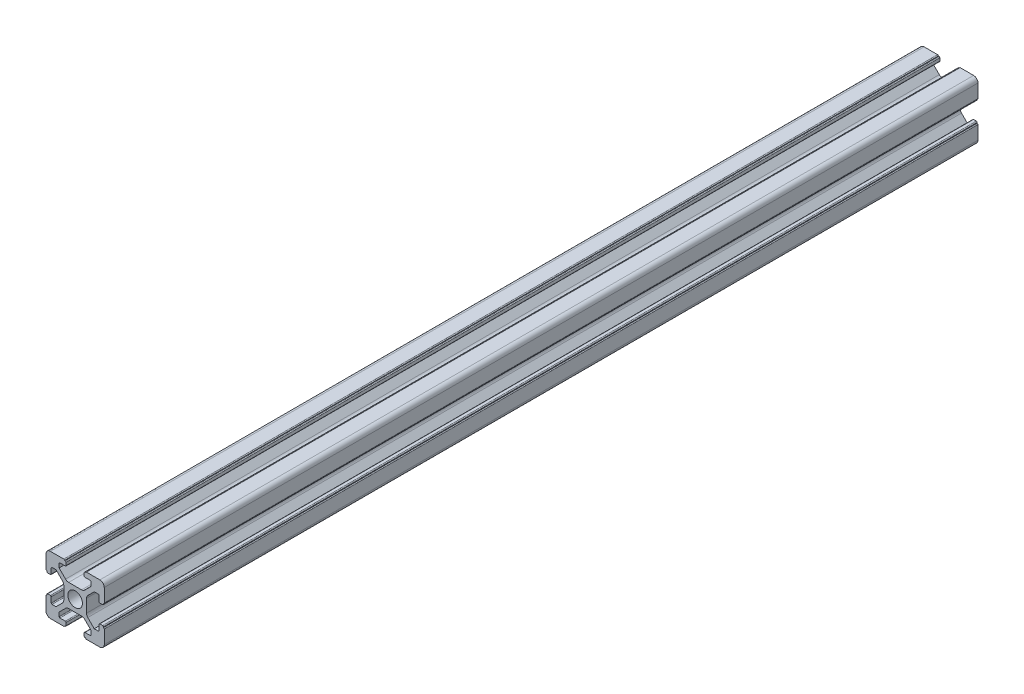
SolidWorks part; units mm, degrees
material "1060 Alloy"
ref_plane "Front Plane" through (0, 0, 0) normal (0, 0, 1) x (1, 0, 0)
ref_plane "Top Plane" through (0, 0, 0) normal (0, 1, 0) x (1, 0, 0)
ref_plane "Right Plane" through (0, 0, 0) normal (1, 0, 0) x (0, 0, -1)
sketch "Sketch1" plane through (0, 0, 0) normal (0, 0, 1) x (1, 0, 0)
  line L0 (3.8995, 3.9005) -> (10.4604, 10.4604) construction
  line L2 (-3.9002, 2.2177) -> (-3.9002, -2.2208)
  line L5 (-3.9005, 3.899) -> (3.9001, -3.8986) construction
  line L6 (-3.9, -3.901) -> (3.8995, 3.9005) construction
  line L7 (-0.0002, 10) -> (-0.0002, -9.9996) construction
  line L8 (-0.0002, -9.9996) -> (-0.0002, 10) construction
  line L9 (5.5006, 6.5619) -> (3.2793, 4.3405)
  line L14 (-10.0002, 9.9996) -> (9.9994, -10) construction
  line L15 (-9.9999, -10.0001) -> (9.9998, 10) construction
  line L16 (6.5613, 5.5012) -> (4.3401, 3.28)
  line L17 (-5.5002, 6.5603) -> (-3.279, 4.3391)
  line L18 (-6.5609, 5.4996) -> (-4.3395, 3.2783)
  line L19 (7.9206, 5.5012) -> (6.5613, 5.5012)
  line L20 (8.2006, 3.3812) -> (8.2006, 5.2212)
  line L21 (9.4206, 3.1012) -> (8.4806, 3.1012)
  line L22 (9.7006, 3.6012) -> (9.7006, 3.3812)
  line L23 (-8.5002, 9.9996) -> (-3.8802, 9.9996)
  line L24 (-3.6002, 9.7196) -> (-3.6002, 9.6996)
  line L25 (-3.6002, 9.6996) -> (-3.3802, 9.6996)
  line L26 (-3.1002, 9.4196) -> (-3.1002, 8.4796)
  line L27 (-3.3802, 8.1996) -> (-5.2202, 8.1996)
  line L28 (-5.5002, 7.9196) -> (-5.5002, 6.5603)
  line L29 (-7.9202, 5.4996) -> (-6.5609, 5.4996)
  line L30 (-8.2002, 3.3796) -> (-8.2002, 5.2196)
  line L31 (-9.4202, 3.0996) -> (-8.4802, 3.0996)
  line L32 (-9.7202, 3.5996) -> (-9.7002, 3.5996)
  line L33 (-9.7002, 3.5996) -> (-9.7002, 3.3796)
  line L34 (-10.0002, 8.4996) -> (-10.0002, 3.8796)
  line L35 (10.0006, 8.5012) -> (10.0006, 3.8812)
  line L36 (8.5006, 10.0012) -> (3.8806, 10.0012)
  line L37 (3.6006, 9.7012) -> (3.3806, 9.7012)
  line L38 (3.1006, 9.4212) -> (3.1006, 8.4812)
  line L39 (3.3806, 8.2012) -> (5.2206, 8.2012)
  line L40 (5.5006, 7.9212) -> (5.5006, 6.5619)
  line L41 (6.5629, -5.4996) -> (4.3415, -3.2783)
  line L42 (5.5022, -6.5603) -> (3.281, -4.3391)
  line L43 (5.5022, -7.9196) -> (5.5022, -6.5603)
  line L44 (3.3822, -8.1996) -> (5.2222, -8.1996)
  line L45 (3.1022, -9.4196) -> (3.1022, -8.4796)
  line L46 (3.6022, -9.6996) -> (3.3822, -9.6996)
  line L47 (8.5022, -9.9996) -> (3.8822, -9.9996)
  line L48 (10.0022, -8.4996) -> (10.0022, -3.8796)
  line L49 (9.7022, -3.5996) -> (9.7022, -3.3796)
  line L50 (9.4222, -3.0996) -> (8.4822, -3.0996)
  line L51 (8.2022, -3.3796) -> (8.2022, -5.2196)
  line L52 (7.9222, -5.4996) -> (6.5629, -5.4996)
  line L53 (-5.4986, -6.5619) -> (-3.2773, -4.3405)
  line L54 (-6.5593, -5.5012) -> (-4.3395, -3.2814)
  line L55 (-7.9186, -5.5012) -> (-6.5593, -5.5012)
  line L56 (-8.1986, -3.3812) -> (-8.1986, -5.2212)
  line L57 (-9.4186, -3.1012) -> (-8.4786, -3.1012)
  line L58 (-9.6986, -3.6012) -> (-9.6986, -3.3812)
  line L59 (-9.9986, -8.5012) -> (-9.9986, -3.8812)
  line L60 (-8.4986, -10.0012) -> (-3.8786, -10.0012)
  line L61 (-3.5986, -9.7012) -> (-3.3786, -9.7012)
  line L62 (-3.0986, -9.4212) -> (-3.0986, -8.4812)
  line L63 (-3.3786, -8.2012) -> (-5.2186, -8.2012)
  line L64 (-5.4986, -7.9212) -> (-5.4986, -6.5619)
  line L65 (-2.233, 3.8998) -> (2.2187, 3.9012)
  line L66 (3.9008, 2.234) -> (3.9022, -2.2177)
  line L67 (2.235, -3.8998) -> (-2.2167, -3.9012)
  line L68 (3.6006, 9.7212) -> (3.6006, 9.6996)
  line L69 (9.7006, 3.6012) -> (9.7206, 3.6012)
  line L70 (-9.6986, -3.6012) -> (-9.7186, -3.6012)
  line L71 (-3.5986, -9.7012) -> (-3.5986, -9.7212)
  line L72 (3.6022, -9.6996) -> (3.6022, -9.7196)
  line L73 (9.7222, -3.5996) -> (9.7022, -3.5996)
  arc A0 (-3.6002, 9.7196) -> (-3.8802, 9.9996) centre (-3.8802, 9.7196) ccw
  arc A1 (-3.3802, 9.6996) -> (-3.1002, 9.4196) centre (-3.3802, 9.4196) cw
  arc A2 (-3.1002, 8.4796) -> (-3.3802, 8.1996) centre (-3.3802, 8.4796) cw
  arc A3 (-10.0002, 8.4996) -> (-8.5002, 9.9996) centre (-8.5002, 8.4996) cw
  arc A4 (-8.2002, 3.3796) -> (-8.4802, 3.0996) centre (-8.4802, 3.3796) cw
  arc A5 (-9.4202, 3.0996) -> (-9.7002, 3.3796) centre (-9.4202, 3.3796) cw
  arc A6 (-9.7202, 3.5996) -> (-10.0002, 3.8796) centre (-9.7202, 3.8796) cw
  arc A7 (-3.279, 4.3391) -> (-2.233, 3.8998) centre (-2.2183, 5.3997) ccw
  arc A8 (-4.3395, 3.2783) -> (-3.9002, 2.2177) centre (-5.4002, 2.2177) cw
  arc A9 (-7.9202, 5.4996) -> (-8.2002, 5.2196) centre (-7.9202, 5.2196) ccw
  arc A10 (-5.2202, 8.1996) -> (-5.5002, 7.9196) centre (-5.2202, 7.9196) ccw
  arc A12 (-4.3395, -3.2814) -> (-3.9002, -2.2208) centre (-5.4002, -2.2208) ccw
  arc A13 (8.2006, 5.2212) -> (7.9206, 5.5012) centre (7.9206, 5.2212) ccw
  arc A14 (8.4806, 3.1012) -> (8.2006, 3.3812) centre (8.4806, 3.3812) cw
  arc A15 (9.7006, 3.3812) -> (9.4206, 3.1012) centre (9.4206, 3.3812) cw
  arc A16 (9.7206, 3.6012) -> (10.0006, 3.8812) centre (9.7206, 3.8812) ccw
  arc A17 (8.5006, 10.0012) -> (10.0006, 8.5012) centre (8.5006, 8.5012) cw
  arc A18 (3.6006, 9.7212) -> (3.8806, 10.0012) centre (3.8806, 9.7212) cw
  arc A19 (3.1006, 9.4212) -> (3.3806, 9.7012) centre (3.3806, 9.4212) cw
  arc A20 (3.3806, 8.2012) -> (3.1006, 8.4812) centre (3.3806, 8.4812) cw
  arc A21 (5.5006, 7.9212) -> (5.2206, 8.2012) centre (5.2206, 7.9212) ccw
  arc A22 (3.2793, 4.3405) -> (2.2187, 3.9012) centre (2.2187, 5.4012) cw
  arc A23 (4.3401, 3.28) -> (3.9008, 2.234) centre (5.4007, 2.2193) ccw
  arc A25 (5.2222, -8.1996) -> (5.5022, -7.9196) centre (5.2222, -7.9196) ccw
  arc A26 (3.1022, -8.4796) -> (3.3822, -8.1996) centre (3.3822, -8.4796) cw
  arc A27 (3.3822, -9.6996) -> (3.1022, -9.4196) centre (3.3822, -9.4196) cw
  arc A28 (3.6022, -9.7196) -> (3.8822, -9.9996) centre (3.8822, -9.7196) ccw
  arc A29 (10.0022, -8.4996) -> (8.5022, -9.9996) centre (8.5022, -8.4996) cw
  arc A30 (9.7222, -3.5996) -> (10.0022, -3.8796) centre (9.7222, -3.8796) cw
  arc A31 (9.4222, -3.0996) -> (9.7022, -3.3796) centre (9.4222, -3.3796) cw
  arc A32 (8.2022, -3.3796) -> (8.4822, -3.0996) centre (8.4822, -3.3796) cw
  arc A33 (7.9222, -5.4996) -> (8.2022, -5.2196) centre (7.9222, -5.2196) ccw
  arc A34 (4.3415, -3.2783) -> (3.9022, -2.2177) centre (5.4022, -2.2177) cw
  arc A35 (3.281, -4.3391) -> (2.235, -3.8998) centre (2.2203, -5.3997) ccw
  circle A36 centre (0.001, -0.001) radius 2.5 construction
  arc A37 (-8.1986, -5.2212) -> (-7.9186, -5.5012) centre (-7.9186, -5.2212) ccw
  arc A38 (-8.4786, -3.1012) -> (-8.1986, -3.3812) centre (-8.4786, -3.3812) cw
  arc A39 (-9.6986, -3.3812) -> (-9.4186, -3.1012) centre (-9.4186, -3.3812) cw
  arc A40 (-9.7186, -3.6012) -> (-9.9986, -3.8812) centre (-9.7186, -3.8812) ccw
  arc A41 (-8.4986, -10.0012) -> (-9.9986, -8.5012) centre (-8.4986, -8.5012) cw
  arc A42 (-3.5986, -9.7212) -> (-3.8786, -10.0012) centre (-3.8786, -9.7212) cw
  arc A43 (-3.0986, -9.4212) -> (-3.3786, -9.7012) centre (-3.3786, -9.4212) cw
  arc A44 (-3.3786, -8.2012) -> (-3.0986, -8.4812) centre (-3.3786, -8.4812) cw
  arc A45 (-5.4986, -7.9212) -> (-5.2186, -8.2012) centre (-5.2186, -7.9212) ccw
  arc A46 (-3.2773, -4.3405) -> (-2.2167, -3.9012) centre (-2.2167, -5.4012) cw
  arc A48 (-4.3381, -3.28) -> (-3.8988, -2.234) centre (-5.3987, -2.2193) ccw [skipped]
  point P0 (0, 0)
  point P9 (-0.0002, 0.0002)
  point P12 (-0.0003, -0.0003)
  point P43 (-3.6002, 9.9996)
  point P46 (-3.1002, 9.6996)
  point P49 (-3.1002, 8.1996)
  point P55 (-8.2002, 3.0996)
  point P58 (-9.7002, 3.0996)
  point P61 (-10.0002, 3.5996)
  point P64 (-2.8395, 3.8996)
  point P67 (-3.9002, 2.839)
  point P70 (-8.2002, 5.4996)
  point P73 (-5.5002, 8.1996)
  point P184 (0.001, 0)
  dimension "D14" = 0.28
  dimension "D15" = 0.28
  dimension "D16" = 0.28
  dimension "D17" = 1.5
  dimension "D18" = 0.28
  dimension "D19" = 1.5
  dimension "D20" = 1.5
  dimension "D21" = 0.28
  dimension "D23" = 5
  dimension "D27" = 1.5
  dimension "D1" = 7.8
  dimension "D2" = 7.8
  dimension "D3" = 3.1
  dimension "D4" = 3.6
  dimension "D5" = 20
  dimension "D6" = 20
  dimension "D7" = 0.75
  dimension "D8" = 1.8
  dimension "D9" = 5.5
  dimension "D10" = 6.4
  dimension "D11" = 6.4
  dimension "D12" = 3.7627
  dimension "D13" = 0.3
  dimension "D24" = 4.62
  dimension "D25" = 3.9005
  dimension "D26" = 7.801
  dimension "D22" = 4
extrude "Boss-Extrude1" add sketch "Sketch1" along normal blind 300 contours L53 A46 L67 A35 L42 L43 A25 L44 A26 L45 A27 L46 L72 A28 L47 A29 L48 A30 L73 L49 A31 L50 A32 L51 A33 L52 L41 A34 L66 A23 L16 L19 A13 L20 A14 L21 A15 L22 L69 A16 L35 A17 L36 A18 L68 L37 A19 L38 A20 region at (0.0009, 0, 0)
sketch3d "3DSketch2"
  circle A0 centre (0, 0, 0) radius 2.5
  point P2 (0, 0, 2.5)
extrude "Cut-Extrude1" cut sketch "3DSketch2" along direction (0, 0, 1) on the side of the normal through all contours A0
